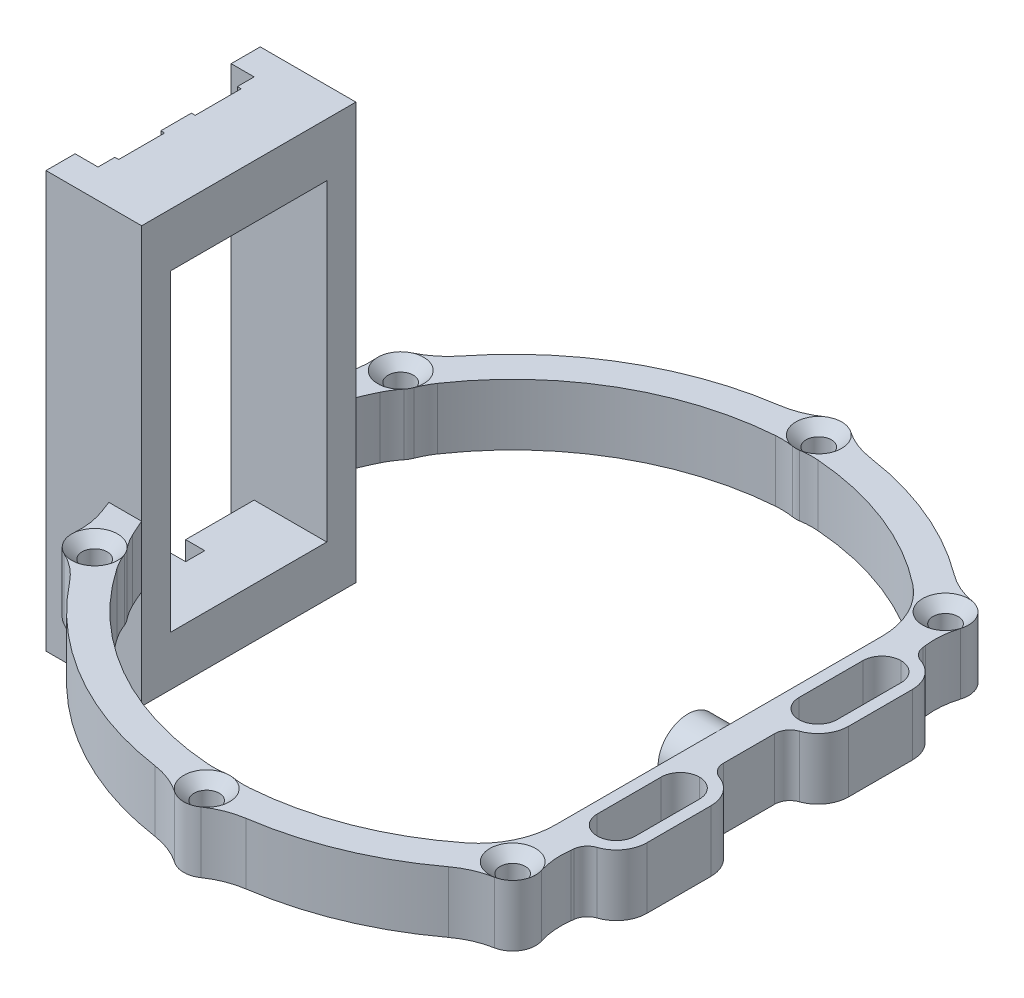
SolidWorks part; units mm, degrees
ref_plane "Front Plane" through (0, 0, 0) normal (0, 0, 1) x (1, 0, 0)
ref_plane "Top Plane" through (0, 0, 0) normal (0, 1, 0) x (1, 0, 0)
ref_plane "Right Plane" through (0, 0, 0) normal (1, 0, 0) x (0, 0, -1)
ref_plane "Plane1" through (-34.5, 0, 0) normal (1, 0, 0) x (0, 0, -1)
ref_plane "Plane2" through (0, -9.75, 0) normal (0, 1, 0) x (1, 0, 0)
sketch "Sketch1" plane through (-34.5, 0, 0) normal (1, 0, 0) x (0, 0, -1)
  line L0 (55, -9.75) -> (-55, -9.75) construction
  line L1 (-10, -9.75) -> (10, -9.75)
  line L2 (-10, -9.75) -> (-10, 30.25)
  line L3 (-10, 30.25) -> (10, 30.25)
  line L4 (10, -9.75) -> (10, 30.25)
  line L5 (0, 55) -> (0, -55) construction
  dimension "D1" = 20
  dimension "D2" = 40
  dimension "D3" = 10
ref_plane "Plane3" through (-44, 0, 0) normal (1, 0, 0) x (0, 0, -1)
sketch "Sketch2" plane through (-44, 0, 0) normal (1, 0, 0) x (0, 0, -1)
  line L0 (0, 22) -> (0, -22) construction
  line L1 (-10, 37.25) -> (10, 37.25)
  line L2 (-10, 37.25) -> (-10, -16.75)
  line L3 (-10, -16.75) -> (10, -16.75)
  line L4 (10, 37.25) -> (10, -16.75)
  line L5 (-10, 37.25) -> (10, -16.75) construction
  line L6 (-10, -16.75) -> (10, 37.25) construction
  line L7 (-10, 30.25) -> (10, 30.25) construction
  line L9 (5, -13.75) -> (-5, -13.75) construction
  line L10 (5, -13.75) -> (5, 34.25) construction
  line L11 (5, 34.25) -> (-5, 34.25) construction
  line L12 (-5, -13.75) -> (-5, 34.25) construction
  line L13 (5, -13.75) -> (-5, 34.25) construction
  line L14 (5, 34.25) -> (-5, -13.75) construction
  circle A0 centre (-5, 34.25) radius 2.25
  circle A1 centre (5, 34.25) radius 2.25
  circle A2 centre (-5, -13.75) radius 2.25
  circle A3 centre (5, -13.75) radius 2.25
  point P0 (0, 10.25)
  point P9 (0, 10.25)
  dimension "D6" = 4.5
  dimension "D1" = 54
  dimension "D2" = 20
  dimension "D3" = 7
  dimension "D4" = 4
  dimension "D5" = 10
ref_plane "Plane4" through (26.5, 0, 0) normal (1, 0, 0) x (0, 0, -1)
ref_plane "Plane5" through (-26.5, 0, 0) normal (1, 0, 0) x (0, 0, -1)
sketch "Sketch3" plane through (-26.5, 0, 0) normal (1, 0, 0) x (0, 0, -1)
  circle A0 centre (0, 0) radius 10
  dimension "D1" = 20
sketch "Sketch4" plane through (26.5, 0, 0) normal (1, 0, 0) x (0, 0, -1)
  circle A0 centre (0, 0) radius 10
  dimension "D1" = 20
sketch "Sketch5" plane through (0, 0, 0) normal (0, 1, 0) x (1, 0, 0)
  circle A0 centre (0, 0) radius 50
  dimension "D1" = 100
sketch "Sketch6" plane through (-44, 0, 0) normal (1, 0, 0) x (0, 0, -1)
  line L0 (10, 37.25) -> (10, -16.75) construction
  line L1 (-14, -16.75) -> (14, -16.75)
  line L2 (-14, -16.75) -> (-14, 37.25)
  line L3 (-14, 37.25) -> (14, 37.25)
  line L4 (14, -16.75) -> (14, 37.25)
  line L5 (-14, -16.75) -> (14, 37.25) construction
  line L6 (-14, 37.25) -> (14, -16.75) construction
  line L7 (-10, 37.25) -> (10, 37.25) construction
  line L8 (-10, 30.25) -> (10, 30.25) construction
  line L9 (10.2, -9.95) -> (-10.2, -9.95)
  line L10 (10.2, -9.95) -> (10.2, 30.45)
  line L11 (10.2, 30.45) -> (-10.2, 30.45)
  line L12 (-10.2, -9.95) -> (-10.2, 30.45)
  line L13 (10.2, -9.95) -> (-10.2, 30.45) construction
  line L14 (10.2, 30.45) -> (-10.2, -9.95) construction
  line L15 (10, -9.75) -> (10, 30.25) construction
  circle A0 centre (-5, 34.25) radius 2.125
  circle A1 centre (5, 34.25) radius 2.125
  circle A2 centre (-5, -13.75) radius 2.125
  circle A3 centre (5, -13.75) radius 2.125
  point P0 (0, 10.25)
  point P10 (0, 10.25)
  dimension "D5" = 4.25
  dimension "D1" = 4
  dimension "D2" = 0
  dimension "D3" = 0.2
  dimension "D4" = 0.2
extrude "Boss-Extrude1" add sketch "Sketch6" along normal blind 4
sketch "Sketch7" plane through (-40, 0, 0) normal (1, 0, 0) x (0, 0, -1)
  line L1 (14, -16.75) -> (-14, -16.75)
  line L2 (14, -16.75) -> (14, 37.25)
  line L3 (14, 37.25) -> (-14, 37.25)
  line L4 (-14, -16.75) -> (-14, 37.25)
  line L5 (14, -16.75) -> (-14, 37.25) construction
  line L6 (14, 37.25) -> (-14, -16.75) construction
  line L7 (-10.2, -10.45) -> (10.2, -10.45)
  line L8 (-10.2, -10.45) -> (-10.2, 30.45)
  line L9 (-10.2, 30.45) -> (10.2, 30.45)
  line L10 (10.2, -10.45) -> (10.2, 30.45)
  line L11 (-10.2, -10.45) -> (10.2, 30.45) construction
  line L12 (-10.2, 30.45) -> (10.2, -10.45) construction
  circle A0 centre (0, 0) radius 10 construction
  point P0 (0, 10.25)
  point P7 (0, 10)
extrude "Boss-Extrude2" add sketch "Sketch7" along normal blind 5.5
sketch "Sketch8" plane through (-44, 0, 0) normal (-1, 0, 0) x (0, 0, 1)
  line L1 (-14, 37.25) -> (-10.2, 37.25)
  line L2 (-14, 37.25) -> (-14, -9.95)
  line L3 (-14, -9.95) -> (-10.2, -9.95)
  line L4 (-10.2, 37.25) -> (-10.2, -9.95)
  line L5 (-10.2, -9.95) -> (-14, -9.95)
  line L6 (-10.2, -9.95) -> (-10.2, -16.75)
  line L7 (-10.2, -16.75) -> (-14, -16.75)
  line L8 (-14, -9.95) -> (-14, -16.75)
  line L9 (14, -16.75) -> (10.2, -16.75)
  line L10 (14, -16.75) -> (14, 30.45)
  line L11 (14, 30.45) -> (10.2, 30.45)
  line L12 (10.2, -16.75) -> (10.2, 30.45)
  line L13 (10.2, 30.45) -> (14, 30.45)
  line L14 (10.2, 30.45) -> (10.2, 37.25)
  line L15 (10.2, 37.25) -> (14, 37.25)
  line L16 (14, 30.45) -> (14, 37.25)
  line M3 (-14, 37.25) -> (-14, -16.75)
  line M4 (-14, -16.75) -> (14, -16.75)
  line M5 (14, -16.75) -> (14, 37.25)
  line M6 (14, 37.25) -> (-14, 37.25)
  line M8 (10.2, 30.45) -> (10.2, -9.95)
  line M10 (-10.2, -9.95) -> (-10.2, 30.45)
extrude "Boss-Extrude3" add sketch "Sketch8" along normal blind 3 contours L14 L11 M5 M6 | L12 L11 M4 M5 M8 | L4 L3 M6 M3 M10 | L6 L3 M3 M4 region at (-44, 13.65, -12.1) region at (-44, -13.35, -12.1) region at (-44, 33.85, 12.1) region at (-44, 6.85, 12.1)
sketch "Sketch9" plane through (-44, 0, 0) normal (-1, 0, 0) x (0, 0, 1)
  line L0 (10, 37.25) -> (-10, 37.25) construction
  line L1 (-8, 34.25) -> (-2, 34.25)
  line L2 (-8, 34.25) -> (-8, 37.25)
  line L3 (-8, 37.25) -> (-2, 37.25)
  line L4 (-2, 34.25) -> (-2, 37.25)
  line L5 (10, -16.75) -> (-10, -16.75) construction
  line L6 (2, 34.25) -> (8, 34.25)
  line L7 (2, 34.25) -> (2, 37.25)
  line L8 (2, 37.25) -> (8, 37.25)
  line L9 (8, 34.25) -> (8, 37.25)
  line L10 (-8, -13.75) -> (-2, -13.75)
  line L11 (-8, -13.75) -> (-8, -16.75)
  line L12 (-8, -16.75) -> (-2, -16.75)
  line L13 (-2, -13.75) -> (-2, -16.75)
  line L15 (2, -13.75) -> (8, -13.75)
  line L16 (2, -13.75) -> (2, -16.75)
  line L17 (2, -16.75) -> (8, -16.75)
  line L18 (8, -13.75) -> (8, -16.75)
  circle A0 centre (-5, 34.25) radius 3
  circle A1 centre (5, 34.25) radius 3
  circle A2 centre (-5, -13.75) radius 3
  circle A3 centre (5, -13.75) radius 3
  line M5 (10.2, 37.25) -> (-10.2, 37.25)
  circle M6 centre (5, 34.25) radius 2.125
  circle M7 centre (-5, 34.25) radius 2.125
  dimension "D1" = 6
extrude "Cut-Extrude1" cut sketch "Sketch9" against normal blind 0.5 and the other way through all contours A3 L17 L18 | L15 A3 | L15 A3 | A3 L16 L17 | A2 L12 L13 | L10 A2 | A2 L11 L12 | L10 A2 | L1 A0 M7 | L1 M7 | A0 L4 M5 | L1 A0 M7 | L1 M7 | A0 L3 L2 | A1 L9 M5 | L6 A1 M6 | A1 L8 L7 | L6 M6 | L6 A1 M6 | L6 M6 region at (-44, 36.4421, -5) region at (-44, 33.3481, -5) region at (-44, 35.1519, -5) region at (-44, 34.1829, -2.4375) region at (-44, 36.5799, -2.6701) region at (-44, 36.5799, 2.6701) region at (-44, 36.5799, -7.3299) region at (-44, 36.3239, 2.9261) region at (-44, 34.1829, 2.4375) region at (-44, 36.5799, 7.3299) region at (-44, 35.1519, 5) region at (-44, 33.3481, 5) region at (-44, -12.4768, -5) region at (-44, -16.0799, -7.3299) region at (-44, -15.0232, -5) region at (-44, -16.0799, -2.6701) region at (-44, -12.4768, 5) region at (-44, -16.0799, 2.6701) region at (-44, -15.0232, 5) region at (-44, -16.0799, 7.3299)
sketch "Sketch12" plane through (-44, 0, 0) normal (-1, 0, 0) x (0, 0, 1)
  line L0 (-10.2, 30.45) -> (10.2, 30.45) construction
  line L1 (1.25, -16.45) -> (-1.25, -16.45)
  line L2 (1.25, -16.45) -> (1.25, 36.95)
  line L3 (1.25, 36.95) -> (-1.25, 36.95)
  line L4 (-1.25, -16.45) -> (-1.25, 36.95)
  line L5 (1.25, -16.45) -> (-1.25, 36.95) construction
  line L6 (1.25, 36.95) -> (-1.25, -16.45) construction
  point P0 (0, 10.25)
  dimension "D1" = 6.5
  dimension "D2" = 2.5
extrude "Cut-Extrude2" cut sketch "Sketch12" against normal blind 2.5
sketch "Sketch13" plane through (0, 0, 0) normal (0, 1, 0) x (1, 0, 0)
  circle A0 centre (0, 0) radius 37.2324
  circle A1 centre (0, 0) radius 41.2324
  dimension "D1" = 4
extrude "Boss-Extrude5" add sketch "Sketch13" along normal blind 4 and the other way blind 4
sketch "Sketch14" plane through (0, 37.25, 0) normal (0, 1, 0) x (1, 0, 0)
  line L0 (-34.5, -29.7) -> (-34.5, 29.7) construction
  line L1 (-47, 14) -> (-34.5, 14)
  line L2 (-47, 14) -> (-47, -14)
  line L3 (-47, -14) -> (-34.5, -14)
  line L4 (-34.5, 14) -> (-34.5, -14)
  line L5 (-34.5, 14) -> (-34.5, -14) construction
  line L6 (-44, -29.7) -> (-44, 29.7) construction
  line L7 (-47, 10.2) -> (-44, 10.2)
  line L8 (-47, 10.2) -> (-47, -10.2)
  line L9 (-47, -10.2) -> (-44, -10.2)
  line L10 (-44, 10.2) -> (-44, -10.2)
  line L11 (-44, -8) -> (-44, -10.2) construction
  line L13 (-44, 8) -> (-43.5, 8)
  line L14 (-44, 8) -> (-44, 2)
  line L15 (-44, 2) -> (-43.5, 2)
  line L16 (-43.5, 8) -> (-43.5, 2)
  line L17 (-44, -2) -> (-43.5, -2)
  line L18 (-44, -2) -> (-44, -8)
  line L19 (-44, -8) -> (-43.5, -8)
  line L20 (-43.5, -2) -> (-43.5, -8)
  line M1 (-44, -2) -> (-43.5, -2)
  line M2 (-43.5, -2) -> (-43.5, -8)
  line M3 (-43.5, -8) -> (-44, -8)
  line M4 (-44, -8) -> (-44, -10.2)
  line M5 (-44, -10.2) -> (-47, -10.2)
  line M6 (-47, -10.2) -> (-47, -14)
  line M7 (-47, -14) -> (-34.5, -14)
  line M8 (-34.5, -14) -> (-34.5, 14)
  line M9 (-34.5, 14) -> (-47, 14)
  line M10 (-47, 14) -> (-47, 10.2)
  line M11 (-47, 10.2) -> (-44, 10.2)
  line M12 (-44, 10.2) -> (-44, 8)
  line M13 (-44, 8) -> (-43.5, 8)
  line M14 (-43.5, 8) -> (-43.5, 2)
  line M15 (-43.5, 2) -> (-44, 2)
  line M16 (-44, 2) -> (-44, -2)
extrude "Boss-Extrude6" add sketch "Sketch14" along normal blind 0.2 contours M16 M1 M2 M3 M4 M5 M6 M7 M8 M9 M10 M11 M12 M13 M14 M15 region at (-39.6584, 37.25, 0)
sketch "Sketch15" plane through (0, -16.75, 0) normal (0, -1, 0) x (1, 0, 0)
  line L1 (-47, 14) -> (-34.5, 14)
  line L2 (-47, 14) -> (-47, -14)
  line L3 (-47, -14) -> (-34.5, -14)
  line L4 (-34.5, 14) -> (-34.5, -14)
  line L5 (-47, 10.2) -> (-44, 10.2)
  line L6 (-47, 10.2) -> (-47, -10.2)
  line L7 (-47, -10.2) -> (-44, -10.2)
  line L8 (-44, 10.2) -> (-44, -10.2)
  line L9 (-44, -8) -> (-43.5, -8)
  line L10 (-44, -8) -> (-44, -2)
  line L11 (-44, -2) -> (-43.5, -2)
  line L12 (-43.5, -8) -> (-43.5, -2)
  line L13 (-44, 8) -> (-43.5, 8)
  line L14 (-44, 8) -> (-44, 2)
  line L15 (-44, 2) -> (-43.5, 2)
  line L16 (-43.5, 8) -> (-43.5, 2)
  line M5 (-44, 2) -> (-44, -2)
  line M6 (-44, -2) -> (-43.5, -2)
  line M7 (-43.5, -2) -> (-43.5, -8)
  line M8 (-43.5, -8) -> (-44, -8)
  line M9 (-44, -8) -> (-44, -10.2)
  line M10 (-44, -10.2) -> (-47, -10.2)
  line M11 (-47, -10.2) -> (-47, -14)
  line M12 (-47, -14) -> (-34.5, -14)
  line M13 (-34.5, -14) -> (-34.5, 14)
  line M14 (-34.5, 14) -> (-47, 14)
  line M15 (-47, 14) -> (-47, 10.2)
  line M16 (-47, 10.2) -> (-44, 10.2)
  line M17 (-44, 10.2) -> (-44, 8)
  line M18 (-44, 8) -> (-43.5, 8)
  line M19 (-43.5, 8) -> (-43.5, 2)
  line M20 (-43.5, 2) -> (-44, 2)
extrude "Boss-Extrude7" add sketch "Sketch15" along normal blind 0.2 contours M20 M5 M6 M7 M8 M9 M10 M11 M12 M13 M14 M15 M16 M17 M18 M19 region at (-39.6584, -16.75, 0)
sketch "Sketch16" plane through (0, 0, 0) normal (0, 1, 0) x (1, 0, 0)
  line L0 (26.9, 25.7418) -> (26.9, -25.7418)
  line L1 (30.9, -20.7711) -> (30.9, 20.7711)
  line L2 (26.5, -29.92) -> (26.5, 29.92) construction
  arc A0 (-34.5, -14) -> (-34.5, 14) centre (0, 0) ccw construction
  arc A1 (26.9, 25.7418) -> (26.9, -25.7418) centre (0, 0) cw
  dimension "D1" = 0.4
  dimension "D2" = 4
extrude "Boss-Extrude8" add sketch "Sketch16" along normal blind 4 and the other way blind 4 contours A1 L0 L1 region at (28.8295, 0, 0)
sketch "Sketch17" plane through (26.9, 0, 0) normal (-1, 0, 0) x (0, 0, 1)
  circle A0 centre (0, 0) radius 3.9
  dimension "D1" = 7.8
extrude "Boss-Extrude9" add sketch "Sketch17" along normal blind 4
sketch "Sketch18" plane through (0, 4, 0) normal (0, 1, 0) x (1, 0, 0)
  line L0 (30.9, -20.7711) -> (30.9, 20.7711) construction
  line L1 (30.9, 45.394) -> (78.9762, 45.394)
  line L2 (30.9, 45.394) -> (30.9, -59.0428)
  line L3 (30.9, -59.0428) -> (78.9762, -59.0428)
  line L4 (78.9762, 45.394) -> (78.9762, -59.0428)
  dimension "D1" = 0
extrude "Cut-Extrude3" cut sketch "Sketch18" against normal through all
fillet "Fillet1" radius 10 2 edges at (26.9, 0, 25.7418) (26.9, 0, -25.7418)
fillet "Fillet2" radius 14 2 edges at (30.9, 0, 27.3002) (30.9, 0, -27.3002)
sketch "Sketch19" plane through (-34.5, 0, 0) normal (1, 0, 0) x (0, 0, -1)
  line L1 (-10.2, 30.45) -> (10.2, 30.45)
  line L2 (-10.2, 30.45) -> (-10.2, -10.45)
  line L3 (-10.2, -10.45) -> (10.2, -10.45)
  line L4 (10.2, 30.45) -> (10.2, -10.45)
extrude "Cut-Extrude4" cut sketch "Sketch19" against normal through all
sketch "Sketch20" plane through (0, 0, 0) normal (0, 1, 0) x (1, 0, 0)
  line L0 (0, 0) -> (28.2843, 28.2843) construction
  line L1 (0, 0) -> (0, 26.0692) construction
  line L2 (0, 0) -> (-34.641, 20) construction
  line L3 (0, 0) -> (9.6679, 0)
  circle A0 centre (0, 0) radius 45
  circle A1 centre (28.2843, 28.2843) radius 3
  circle A2 centre (28.2843, 28.2843) radius 1.65
  circle A3 centre (40, 0) radius 1.65
  circle A4 centre (40, 0) radius 3
  circle A5 centre (28.2843, -28.2843) radius 1.65
  circle A6 centre (28.2843, -28.2843) radius 3
  circle A7 centre (0, -40) radius 1.65
  circle A8 centre (0, -40) radius 3
  circle A9 centre (-28.2843, -28.2843) radius 1.65
  circle A10 centre (-28.2843, -28.2843) radius 3
  circle A11 centre (-40, 0) radius 1.65
  circle A12 centre (-40, 0) radius 3
  circle A13 centre (-28.2843, 28.2843) radius 1.65
  circle A14 centre (-28.2843, 28.2843) radius 3
  circle A15 centre (0, 40) radius 1.65
  circle A16 centre (0, 40) radius 3
  circle A17 centre (-34.641, 20) radius 3
  circle A18 centre (-34.641, 20) radius 1.65
  circle A19 centre (-34.641, -20) radius 1.65
  circle A20 centre (-34.641, -20) radius 3
  point P19 (0, 0)
  dimension "D1" = 90
  dimension "D2" = 45
  dimension "D4" = 3.3
  dimension "D5" = 6
  dimension "D9" = 6
  dimension "D10" = 3.3
  dimension "D3" = 40
  dimension "D7" = 40
  dimension "D8" = 60
  dimension "D6" = 8
extrude "Boss-Extrude10" add sketch "Sketch20" along normal blind 4 and the other way blind 4 contours A1 A2 | A6 A5 | A8 A7 | A16 A15 | A17 A18 | A20 A19 region at (25.3691, 0, -28.2843) region at (25.3691, 0, 28.2843) region at (-2.9151, 0, 40) region at (-2.9151, 0, -40) region at (-37.5562, 0, -20) region at (-37.5562, 0, 20)
sketch "Sketch21" plane through (0, 4, 0) normal (0, 1, 0) x (1, 0, 0)
  circle A0 centre (0, -40) radius 1.65
  circle A4 centre (-10.3528, -38.637) radius 1.65
  circle A5 centre (-20, -34.641) radius 1.65
  circle A6 centre (-28.2843, -28.2843) radius 1.65
  circle A7 centre (-34.641, -20) radius 1.65
  circle A8 centre (-38.637, -10.3528) radius 1.65
  circle A9 centre (-40, 0) radius 1.65
  circle A10 centre (-38.637, 10.3528) radius 1.65
  circle A11 centre (-34.641, 20) radius 1.65
  circle A12 centre (-28.2843, 28.2843) radius 1.65
  circle A13 centre (-20, 34.641) radius 1.65
  circle A14 centre (-10.3528, 38.637) radius 1.65
  circle A15 centre (0, 40) radius 1.65
  circle A16 centre (10.3528, 38.637) radius 1.65
  circle A17 centre (20, 34.641) radius 1.65
  circle A18 centre (28.2843, 28.2843) radius 1.65
  circle A19 centre (34.641, 20) radius 1.65
  circle A20 centre (38.637, 10.3528) radius 1.65
  circle A21 centre (40, 0) radius 1.65
  circle A22 centre (38.637, -10.3528) radius 1.65
  circle A23 centre (34.641, -20) radius 1.65
  circle A24 centre (28.2843, -28.2843) radius 1.65
  circle A25 centre (20, -34.641) radius 1.65
  circle A26 centre (10.3528, -38.637) radius 1.65
  point P12 (0, 0)
  point P54 (0, 0)
  arc M29 (-1.1138, -41.2173) -> (1.1138, -41.2173) centre (0, 0) ccw
  arc M31 (29.5875, 27.2723) -> (27.9838, 29.9067) centre (16.9, 21.354) ccw
  arc M37 (27.9838, -29.9067) -> (29.5875, -27.2723) centre (16.9, -21.354) ccw
  arc M49 (-36.2522, -19.6441) -> (-35.1383, -21.5733) centre (0, 0) ccw
  arc M51 (-35.1383, 21.5733) -> (-36.2522, 19.6441) centre (0, 0) ccw
  arc M54 (1.1138, 41.2173) -> (-1.1138, 41.2173) centre (0, 0) ccw
  dimension "D1" = 24
extrude "Cut-Extrude5" cut sketch "Sketch21" against normal through all both and the other way through all contours A15 M54 | A18 M31 | A24 M37 | A0 M29 | A7 M49 | A11 M51 region at (0, 4, 39.887) region at (-34.5432, 4, 19.9435) region at (-34.5432, 4, -19.9435) region at (0, 4, -39.887) region at (27.9699, 4, -28.0929) region at (27.9699, 4, 28.0929)
fillet "Fillet5" radius 10 20 edges at (1.1168, 0, -37.2156) (-1.1168, 0, -37.2156) (1.1168, 0, 37.2156) (-1.1168, 0, 37.2156) (-31.6713, 0, -19.575) (-32.7881, 0, -17.6406) (-31.6713, 0, 19.575) (-32.7881, 0, 17.6406) (30.1337, 0, -25.9222) (27.0353, 0, -31.0119) (2.7754, 0, -41.1389) (-2.7754, 0, -41.1389) (-34.2396, 0, -22.973) (-37.015, 0, -18.1658) (-37.015, 0, 18.1658) (-34.2396, 0, 22.973) (-2.7754, 0, 41.1389) (2.7754, 0, 41.1389) (27.0353, 0, 31.0119) (30.1337, 0, 25.9222)
chamfer "Chamfer1" distance 1.35 angle 45 6 edges at (-34.641, 4, 21.65) (0, 4, 41.65) (28.2843, 4, 29.9343) (28.2843, 4, -26.6343) (0, 4, -38.35) (-34.641, 4, -18.35)
sketch "Sketch22" plane through (0, 4, 0) normal (0, 1, 0) x (1, 0, 0)
  line L1 (30.9, 21.354) -> (34.9, 21.354)
  line L2 (30.9, 21.354) -> (30.9, 5)
  line L3 (30.9, 5) -> (34.9, 5)
  line L4 (34.9, 21.354) -> (34.9, 5)
  line L5 (30.9, -21.354) -> (34.9, -21.354)
  line L6 (30.9, -21.354) -> (30.9, -5)
  line L7 (30.9, -5) -> (34.9, -5)
  line L8 (34.9, -21.354) -> (34.9, -5)
  dimension "D1" = 4
  dimension "D2" = 5
  dimension "D3" = 5
extrude "Boss-Extrude11" add sketch "Sketch22" against normal up to surface (8 mm away) up to face at (-6.0231, -4, 0)
sketch "Sketch23" plane through (0, 4, 0) normal (0, 1, 0) x (1, 0, 0)
  line L19 (34.9, 21.354) -> (30.9, 21.354) construction
  line L20 (28.4, 19.854) -> (33.4, 19.854)
  line L21 (28.4, 19.854) -> (28.4, 6.5)
  line L22 (28.4, 6.5) -> (33.4, 6.5)
  line L23 (33.4, 19.854) -> (33.4, 6.5)
  line L28 (34.9, 5) -> (34.9, 21.354) construction
  line L29 (26.9, 21.354) -> (26.9, -21.354) construction
  line L30 (30.9, 5) -> (34.9, 5) construction
  line L31 (0, 0) -> (5.1019, 0)
  line L32 (28.4, -6.5) -> (33.4, -6.5)
  line L33 (33.4, -19.854) -> (33.4, -6.5)
  line L34 (28.4, -19.854) -> (33.4, -19.854)
  line L35 (28.4, -19.854) -> (28.4, -6.5)
  dimension "D1" = 1.5
  dimension "D2" = 1.5
  dimension "D3" = 1.5
  dimension "D4" = 1.5
extrude "Cut-Extrude6" cut sketch "Sketch23" against normal blind 10 contours L23 L20 L21 L22 | L35 L34 L33 L32 region at (30.9, 4, -13.177) region at (30.9, 4, 13.177)
fillet "Fillet6" radius 2.5 8 edges at (28.4, 0, 19.854) (33.4, 0, 19.854) (33.4, 0, 6.5) (28.4, 0, 6.5) (28.4, 0, -6.5) (33.4, 0, -6.5) (33.4, 0, -19.854) (28.4, 0, -19.854)
fillet "Fillet7" radius 4 4 edges at (34.9, 0, 21.354) (34.9, 0, 5) (34.9, 0, -21.354) (34.9, 0, -5)
fillet "Fillet8" radius 2 4 edges at (30.9, 0, 21.354) (30.9, 0, -21.354) (30.9, 0, 5) (30.9, 0, -5)
